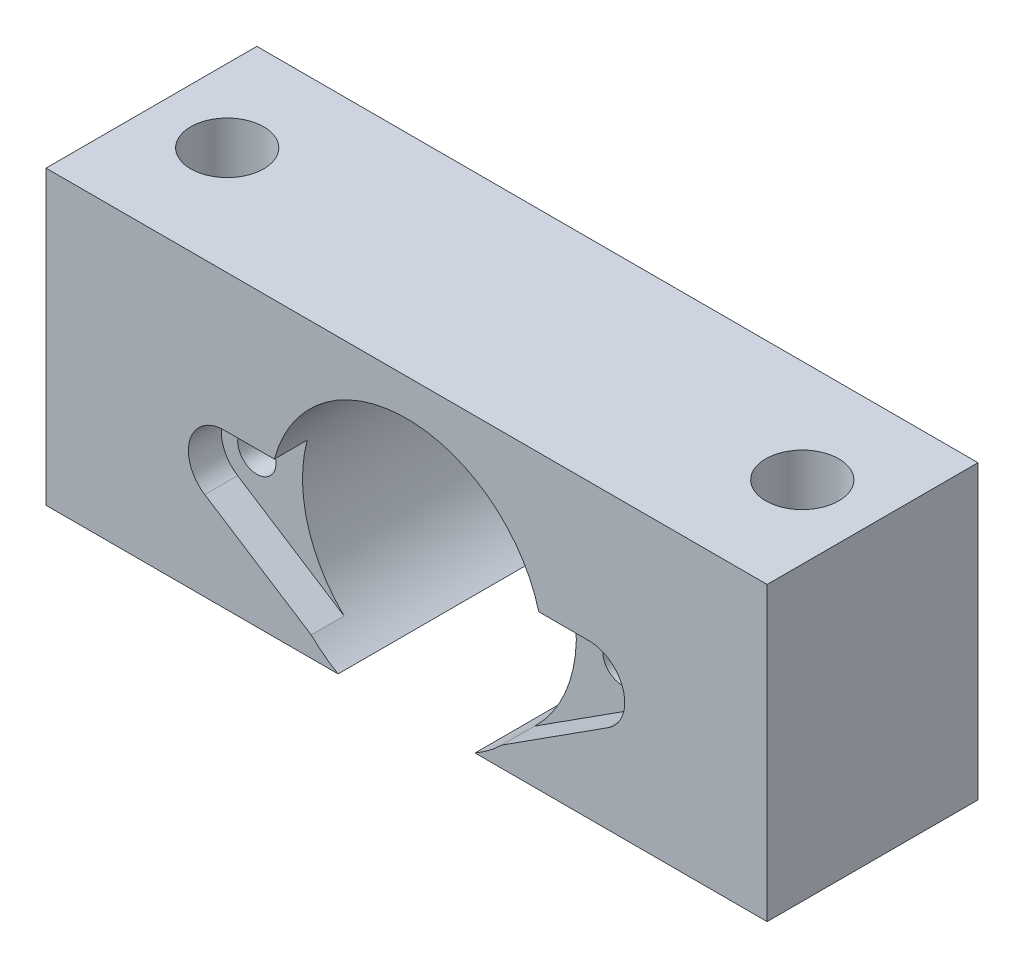
SolidWorks part; units mm, degrees
ref_plane "Front Plane" through (0, 0, 0) normal (0, 0, 1) x (1, 0, 0)
ref_plane "Top Plane" through (0, 0, 0) normal (0, 1, 0) x (1, 0, 0)
ref_plane "Right Plane" through (0, 0, 0) normal (1, 0, 0) x (0, 0, -1)
ref_plane "Plane1" through (-19.75, 1.025, -25.7208) normal (1, 0, 0) x (0, 0, -1)
sketch "BODY" plane through (0, 0, -35.5708) normal (0, 0, 1) x (1, 0, 0)
  line L1 (-3.75, -6.4952) -> (-19.75, -6.4952)
  line L2 (-19.75, -6.4952) -> (-19.75, 9.5)
  line L3 (-19.75, 9.5) -> (19.75, 9.5)
  line L4 (19.75, 9.5) -> (19.75, -6.4952)
  line L5 (19.75, -6.4952) -> (3.75, -6.4952)
  line L6 (-3.75, -6.4952) -> (-11.134, -1.7675)
  line L7 (-10, 2.1) -> (-7.2, 2.1)
  line L9 (10, 2.1) -> (7.2, 2.1)
  line L11 (11.134, -1.7675) -> (3.75, -6.4952)
  arc A0 (-3.75, -6.4952) -> (3.75, -6.4952) centre (0, 0) cw
  arc A1 (-10, 2.1) -> (-11.134, -1.7675) centre (-10, 0) ccw
  arc A3 (10, 2.1) -> (11.134, -1.7675) centre (10, 0) cw
  circle A5 centre (-10, 0) radius 1.05
  circle A6 centre (10, 0) radius 1.05
  point P0 (0, 0)
  point P9 (0, 7.5)
  arc M7 (11.2, 0) -> (8.8, 0) centre (10, 0) cw
  arc M8 (8.8, 0) -> (11.2, 0) centre (10, 0) cw
  arc M9 (-8.8, 0) -> (-11.2, 0) centre (-10, 0) cw
  arc M10 (-11.2, 0) -> (-8.8, 0) centre (-10, 0) cw
  line M18 (3.969, -6.1862) -> (11.053, -1.6412)
  arc M19 (11.053, -1.6412) -> (11.95, 0) centre (10, 0) ccw
  arc M20 (11.95, 0) -> (10, 1.95) centre (10, 0) ccw
  line M21 (10, 1.95) -> (6.6337, 1.95)
  line M27 (-6.6337, 1.95) -> (-10, 1.95)
  arc M28 (-10, 1.95) -> (-11.053, -1.6412) centre (-10, 0) ccw
  line M29 (-11.053, -1.6412) -> (-3.969, -6.1862)
  dimension "D1" = 2
extrude "Body Extrude" add sketch "BODY" against normal blind 11.55 contours L5 A0 L1 L2 L3 L4
extrude "Wings Cut Extrude" cut sketch "BODY<4>" against normal blind 1.8 contours A0 M21 M18 M19 M20 M8 M7 | A6 M7 M8 | A5 M9 M10 | A0 M29 M27 M28 M10 M9 region at (-8.8701, -0.9097, -35.5708) region at (8.8701, -0.9097, -35.5708) region at (10, -1.1661, -35.5708) region at (-10, -1.1661, -35.5708)
sketch "BODY<4>" plane through (0, 0, -35.5708) normal (0, 0, 1) x (1, 0, 0) same geometry as "BODY"
extrude "Screw Holes Cut Extrude" cut sketch "BODY<5>" against normal blind 6 contours A6 | A5 region at (-10, 0, -35.5708) region at (10, 0, -35.5708)
sketch "BODY<5>" plane through (0, 0, -35.5708) normal (0, 0, 1) x (1, 0, 0) same geometry as "BODY"
sketch "ADJUSTMENT SCREW HOLES" plane through (0, 9.5, 0) normal (0, 1, 0) x (1, 0, 0)
  line L2 (-19.75, 47.1208) -> (-19.75, 35.5708) construction
  line L3 (19.75, 47.1208) -> (19.75, 35.5708) construction
  line L4 (-19.75, 47.1208) -> (19.75, 47.1208) construction
  circle A2 centre (-15.75, 41.4958) radius 2
  circle A3 centre (15.75, 41.4958) radius 2
  point P9 (0, 0)
  point P10 (0, 0)
  point P11 (0, 0)
  point P12 (0, 0)
  point P13 (0, 0)
  dimension "D1" = 4
  dimension "D2" = 4
  dimension "D3" = 5.625
  dimension "D4" = 5.625
extrude "Adjustment Screw Holes Cut Extrude" cut sketch "ADJUSTMENT SCREW HOLES" against normal up to vertex (15.9952 mm away) up to point (-19.75, -6.4952, -47.1208)
